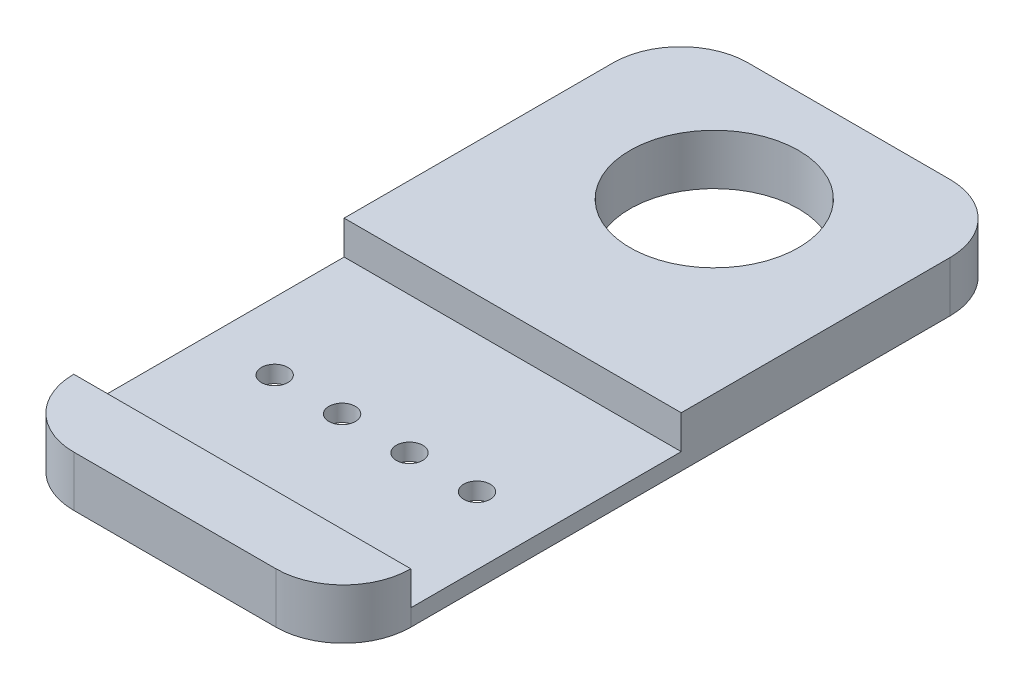
SolidWorks part; units mm, degrees
ref_plane "Front Plane" through (0, 0, 0) normal (0, 0, 1) x (1, 0, 0)
ref_plane "Top Plane" through (0, 0, 0) normal (0, 1, 0) x (1, 0, 0)
ref_plane "Right Plane" through (0, 0, 0) normal (1, 0, 0) x (0, 0, -1)
sketch "Sketch1" plane through (0, 0, 0) normal (0, 1, 0) x (1, 0, 0)
  line L0 (0, -111.3091) -> (63.5, -111.3091)
  line L1 (0, 2.9909) -> (63.5, 2.9909)
  line L2 (0, 2.9909) -> (0, -124.0091)
  line L3 (0, -124.0091) -> (63.5, -124.0091)
  line L4 (63.5, 2.9909) -> (63.5, -124.0091)
  line L7 (0, -60.3821) -> (63.5, -60.3821)
  circle A0 centre (31.75, -22.4091) radius 15.875
  circle A1 centre (12.7, -86.1631) radius 2.4892
  circle A2 centre (25.4, -86.1631) radius 2.4892
  circle A3 centre (38.1, -86.1631) radius 2.4892
  circle A4 centre (50.8, -86.1631) radius 2.4892
  dimension "D3" = 31.75
  dimension "D4" = 25.4
  dimension "D5" = 31.75
  dimension "D6" = 4.9784
  dimension "D7" = 12.7
  dimension "D8" = 37.846
  dimension "D1" = 63.5
  dimension "D2" = 127
  dimension "D10" = 12.7
  dimension "D12" = 63.627
  dimension "D9" = 4
extrude "Boss-Extrude2" add sketch "Sketch1" along normal blind 9.525 contours L4 L0 L2 L3 | L2 L7 L4 L1 A0 region at (31.75, 0, 117.6591) region at (0.8971, 0, 28.6956)
extrude "Boss-Extrude3" add sketch "Sketch1<3>" along normal blind 3.175 contours L7 L2 L0 L4 A4 A3 A2 A1 region at (31.75, 0, 85.8377)
sketch "Sketch1<3>" plane through (0, 0, 0) normal (0, 1, 0) x (1, 0, 0) same geometry as "Sketch1"
fillet "Fillet2" radius 12.7 4 edges at (0, 4.7625, 124.0091) (63.5, 4.7625, 124.0091) (0, 4.7625, -2.9909) (63.5, 4.7625, -2.9909)
